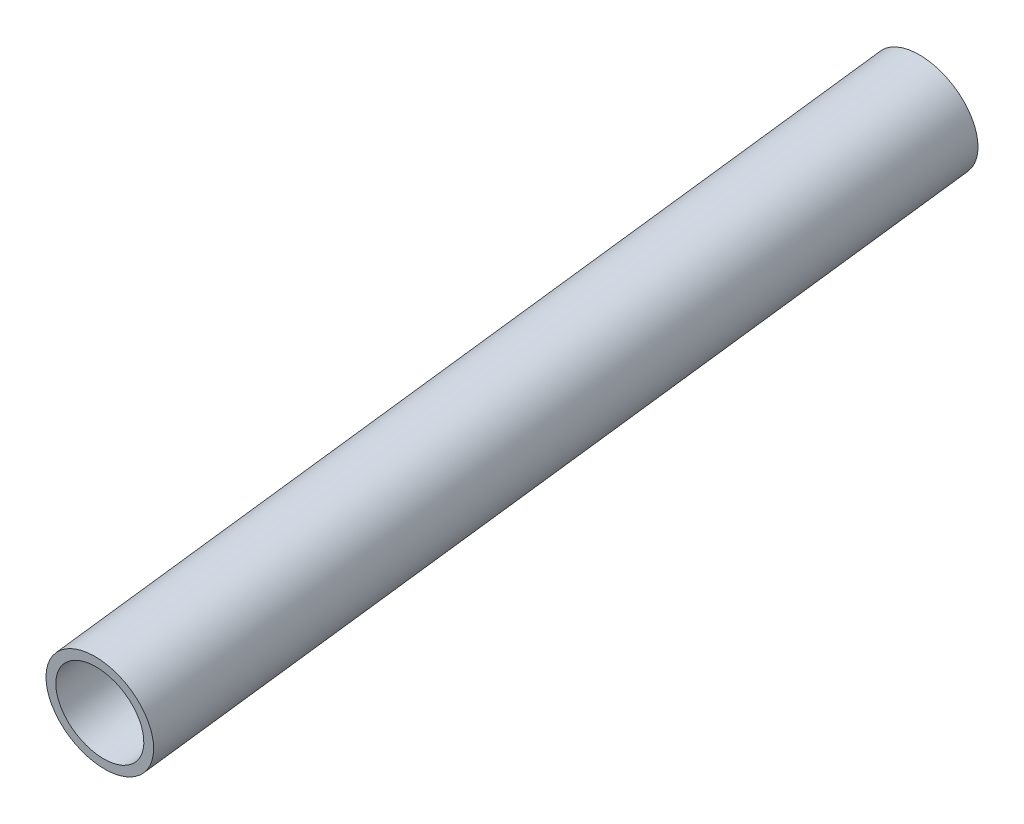
SolidWorks part; units mm, degrees
material "AISI 4130 Steel, annealed at 865C"
ref_plane "X-Y Datum" through (0, 0, 0) normal (0, 0, 1) x (1, 0, 0)
ref_plane "X-Z Datum" through (0, 0, 0) normal (0, 1, 0) x (1, 0, 0)
ref_plane "Y-Z Datum" through (0, 0, 0) normal (1, 0, 0) x (0, 0, -1)
ref_plane "Plane1" through (-799.0943, 449.1429, 290.9609) normal (-0.0169, 0.112, -0.9936) x (0.9998, 0.0055, -0.0164)
sketch "Sketch1" plane through (-799.0943, 449.1429, 290.9609) normal (-0.0169, 0.112, -0.9936) x (0.9998, 0.0055, -0.0164)
  circle A0 centre (0, 0) radius 6.35
  dimension "D1" = 12.7
extrude "Boss-Extrude1" add sketch "Sketch1" along normal up to surface (50.9399 mm away) and the other way up to surface (50.9399 mm away) contours A0
sketch "Sketch2" plane through (2.9518, -19.5264, 173.1747) normal (-0.0169, 0.112, -0.9936) x (0.9998, 0.0055, -0.0164)
  circle A0 centre (-801.2691, -481.846) radius 5.1943
  dimension "D1" = 10.3886
extrude "Cut-Extrude1" cut sketch "Sketch2" against normal through all
